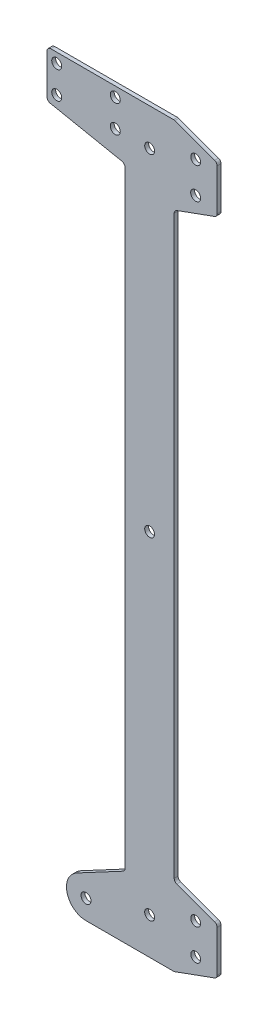
SolidWorks part; units mm, degrees
ref_plane "Front Plane" through (0, 0, 0) normal (0, 0, 1) x (1, 0, 0)
ref_plane "Top Plane" through (0, 0, 0) normal (0, 1, 0) x (1, 0, 0)
ref_plane "Right Plane" through (0, 0, 0) normal (1, 0, 0) x (0, 0, -1)
sketch "Sketch1" plane through (0, 0, 0) normal (0, 0, 1) x (1, 0, 0)
  line L1 (-10, 150) -> (10, 150)
  line L2 (-10, 150) -> (-10, -150)
  line L3 (-10, -150) -> (10, -150)
  line L4 (10, 150) -> (10, -150)
  line L5 (-10, 150) -> (10, -150) construction
  line L6 (-10, -150) -> (10, 150) construction
  point P0 (0, 0)
  dimension "D1" = 300
  dimension "20mm" = 20
extrude "Boss-Extrude1" add sketch "Sketch1" along normal blind 1.5875
sketch "Sketch2" plane through (0, 0, 1.5875) normal (0, 0, 1) x (1, 0, 0)
  line L0 (10, 150) -> (27.4625, 143.65)
  line L1 (27.4625, 143.65) -> (27.4625, 124.6)
  line L2 (27.4625, 124.6) -> (10, 118.25)
  line L3 (10, -150) -> (10, 150) construction
  line L4 (10, 118.25) -> (10, 150)
  line L5 (10, 150) -> (-10, 150) construction
  line L6 (-10, 0) -> (10, 0) construction
  line L7 (-10, 150) -> (-10, -150) construction
  line L8 (10, -118.25) -> (10, -150)
  line L9 (27.4625, -124.6) -> (10, -118.25)
  line L10 (27.4625, -143.65) -> (27.4625, -124.6)
  line L11 (10, -150) -> (27.4625, -143.65)
  line L12 (18.7312, 140.475) -> (18.7313, 127.775) construction
  line L13 (18.7313, -127.775) -> (18.7313, -140.475) construction
  circle A1 centre (18.7313, 127.775) radius 5 construction
  circle A2 centre (18.7312, 140.475) radius 2
  circle A4 centre (18.7313, -127.775) radius 5 construction
  circle A5 centre (18.7313, -127.775) radius 2
  circle A6 centre (18.7312, 134.125) radius 2 construction
  circle A7 centre (18.7313, -134.125) radius 2 construction
  circle A8 centre (18.7313, 127.775) radius 2.032
  circle A9 centre (18.7313, -140.475) radius 2
  point P3 (27.4625, 134.125)
  point P8 (10, 134.125)
  point P13 (18.7312, 121.425)
  point P31 (27.4625, -134.125)
  dimension "D3" = 4
  dimension "D4" = 10
  dimension "D7" = 4.064
  dimension "D1" = 17.4625
  dimension "2.5" = 31.75
  dimension "D2" = 19.05
  dimension "D5" = 9.525
  dimension "D6" = 9.525
  dimension "D8" = 12.7
extrude "Boss-Extrude2" add sketch "Sketch2" against normal up to surface (1.5875 mm away) up to face at (0, 0, 0)
sketch "Sketch4" plane through (0, 0, 1.5875) normal (0, 0, 1) x (1, 0, 0)
  line L0 (0, 150) -> (0, 135) construction
  line L2 (0, 135) -> (0, 0) construction
  line L3 (0, 0) -> (0, -135) construction
  line L4 (0, -135) -> (0, -150) construction
  line L6 (10, 150) -> (-10, 150) construction
  line L7 (-10, -150) -> (10, -150) construction
  circle A0 centre (0, -135) radius 2
  circle A1 centre (0, 0) radius 2
  circle A2 centre (0, 135) radius 2
  dimension "D4" = 4
  dimension "D1" = 15
  dimension "D2" = 135
  dimension "D3" = 135
extrude "Cut-Extrude1" cut sketch "Sketch4" against normal through all
sketch "Sketch5" plane through (0, 0, 1.5875) normal (0, 0, 1) x (1, 0, 0)
  line L0 (-10, 124.6) -> (-41.75, 130.95)
  line L1 (-10, 150) -> (-10, -150) construction
  line L2 (-41.75, 130.95) -> (-41.75, 150)
  line L3 (-41.75, 150) -> (-10, 150)
  line L4 (-10, 150) -> (-10, 124.6)
  line L5 (10, 150) -> (-10, 150) construction
  line L6 (-41.75, 146.0313) -> (-37.7813, 146.0313) construction
  line L7 (-13.9688, 146.0313) -> (-10, 146.0313) construction
  line L8 (-10, -150) -> (-25.875, -150)
  line L9 (-29.6103, -135.0588) -> (-10, -124.6)
  line L10 (-10, -124.6) -> (-10, -150)
  circle A0 centre (-13.9688, 146.0313) radius 2.032
  circle A1 centre (-13.9688, 134.9188) radius 2.032
  circle A2 centre (-37.7813, 146.0313) radius 2.032
  circle A3 centre (-37.7813, 134.9188) radius 2.032
  arc A4 (-25.875, -150) -> (-29.6103, -135.0588) centre (-25.875, -142.0625) cw
  circle A5 centre (-25.875, -142.0625) radius 2.032
  point P24 (-25.875, 150)
  dimension "D5" = 4.064
  dimension "D9" = 4.064
  dimension "D10" = 7.9375
  dimension "D1" = 0
  dimension "D2" = 19.05
  dimension "D3" = 25.4
  dimension "D4" = 31.75
  dimension "D6" = 11.1125
  dimension "D7" = 23.8125
  dimension "D8" = 3.9688
  dimension "D11" = 25.4
extrude "Boss-Extrude3" add sketch "Sketch5" against normal up to surface (1.5875 mm away) up to face at (2, -135, 0)
fillet "Fillet3" radius 1.5875 11 edges at (-10, -124.6, 0.7937) (27.4625, -143.65, 0.7937) (27.4625, -124.6, 0.7937) (10, -118.25, 0.7937) (27.4625, 124.6, 0.7937) (10, 118.25, 0.7937) (27.4625, 143.65, 0.7937) (10, 150, 0.7937) (-10, 124.6, 0.7937) (-41.75, 130.95, 0.7937) (-41.75, 150, 0.7937)
sketch "Sketch6" [suppressed] plane through (0, 0, 3.175) normal (0, 0, 1) x (1, 0, 0)
  line L0 (-10, -124.6) -> (-10, -150) construction
  line L1 (-10, -150) -> (-25.875, -150) construction
  line L2 (-29.6103, -135.0588) -> (-10, -124.6) construction
  line L3 (-10, -124.6) -> (-10, -150)
  line L4 (-10, -150) -> (-25.875, -150)
  line L5 (-29.6103, -135.0588) -> (-10, -124.6)
  circle A0 centre (-25.875, -142.0625) radius 2.032 construction
  arc A1 (-29.6103, -135.0588) -> (-25.875, -150) centre (-25.875, -142.0625) ccw construction
  circle A2 centre (-25.875, -142.0625) radius 2.032
  arc A3 (-29.6103, -135.0588) -> (-25.875, -150) centre (-25.875, -142.0625) ccw
extrude "Boss-Extrude4" [suppressed] add sketch "Sketch6" against normal up to vertex up to point (-10, -123.6475, 0)
fillet "Fillet4" [suppressed] radius 0.7937
fillet "Fillet5" [suppressed] radius 1.5875
sketch "Sketch7" [suppressed] plane through (0, 0, 0) normal (0, 0, -1) x (-1, 0, 0)
  line L0 (-27.1212, 143.7462) -> (-65.2212, 117.3147)
  line L1 (-65.5625, 116.6625) -> (-65.5625, 10.1095)
  line L2 (-63.2093, 7.0427) -> (-10, -7.2147)
  line L4 (-10, -7.2147) -> (-10, 124.044)
  line L5 (-27.4625, 143.094) -> (-27.4625, 131.506) construction
  line L6 (-26.94, 130.76) -> (-10.5225, 124.79) construction
  line L7 (-27.4625, 143.094) -> (-27.4625, 131.506)
  line L8 (-26.94, 130.76) -> (-10.5225, 124.79)
  line L9 (-10, 150) -> (9.2063, 150) construction
  line L10 (-10, 150) -> (9.2063, 150) construction
  line L11 (-48.989, 45.225) -> (-48.989, 48.4) construction
  line L12 (-38.6703, 23) -> (-59.3078, 23) construction
  line L13 (-38.6703, 23) -> (-38.6703, 67.45) construction
  line L14 (-38.6703, 67.45) -> (-59.3078, 67.45) construction
  line L15 (-59.3078, 23) -> (-59.3078, 67.45) construction
  line L16 (-38.6703, 23) -> (-59.3078, 67.45) construction
  line L17 (-38.6703, 67.45) -> (-59.3078, 23) construction
  line L18 (-48.989, 99.2) -> (-48.989, 48.4) construction
  line L19 (-10, -124.044) -> (-10, 124.044) construction
  arc A0 (-65.2212, 117.3147) -> (-65.5625, 116.6625) centre (-64.7688, 116.6625) ccw
  arc A1 (-65.5625, 10.1095) -> (-63.2093, 7.0427) centre (-62.3875, 10.1095) ccw
  arc A2 (-26.94, 143.84) -> (-27.4625, 143.094) centre (-26.6688, 143.094) ccw construction
  arc A3 (-27.4625, 131.506) -> (-26.94, 130.76) centre (-26.6688, 131.506) ccw construction
  arc A4 (-10, 124.044) -> (-10.5225, 124.79) centre (-10.7937, 124.044) ccw construction
  arc A5 (-27.1212, 143.7462) -> (-27.4625, 143.094) centre (-26.6688, 143.094) ccw
  arc A6 (-27.4625, 131.506) -> (-26.94, 130.76) centre (-26.6688, 131.506) ccw
  arc A7 (-10, 124.044) -> (-10.5225, 124.79) centre (-10.7937, 124.044) ccw
  arc A8 (10, 149.2063) -> (9.2063, 150) centre (9.2063, 149.2063) ccw construction
  circle A9 centre (-48.989, 99.2) radius 4.7625
  circle A10 centre (-48.989, 48.4) radius 6.985
  circle A11 centre (-59.3078, 67.45) radius 2.032
  circle A12 centre (-59.3078, 23) radius 2.032
  circle A13 centre (-38.6703, 23) radius 2.032
  circle A14 centre (-38.6703, 67.45) radius 2.032
  circle A15 centre (-18.7312, 10.3) radius 2.032
  point P32 (-48.989, 45.225)
  point P45 (-18.7312, 137.3)
  dimension "D4" = 9.525
  dimension "D6" = 13.97
  dimension "D11" = 4.064
  dimension "D15" = 3.175
  dimension "D1" = 38.1
  dimension "D2" = 106.553
  dimension "D3" = 16.5735
  dimension "D5" = 50.8
  dimension "D7" = 3.175
  dimension "D8" = 44.45
  dimension "D9" = 50.8
  dimension "D10" = 20.6375
  dimension "D12" = 75
  dimension "D13" = 127
  dimension "D14" = 33.3375
extrude "Boss-Extrude5" [suppressed] add sketch "Sketch7" against normal up to surface (3.175 mm away) up to face at (2, -135, 1.5875)
sketch "Sketch8" [suppressed] plane through (0, 0, 3.175) normal (0, 0, 1) x (1, 0, 0)
  line L0 (48.989, 48.4) -> (48.989, 67.45) construction
  line L1 (48.989, 48.4) -> (29.939, 48.4) construction
  line L2 (48.989, 48.4) -> (48.989, 29.35) construction
  line L3 (48.989, 99.2) -> (58.514, 99.2) construction
  line L4 (48.989, 99.2) -> (39.464, 99.2) construction
  line L5 (19.6203, 67.45) -> (19.6203, 54.75) construction
  circle A0 centre (48.989, 67.45) radius 2.032
  circle A1 centre (29.939, 48.4) radius 2.032
  circle A2 centre (48.989, 29.35) radius 2.032
  circle A3 centre (59.3078, 67.45) radius 2.032 construction
  circle A4 centre (58.514, 99.2) radius 2.032
  circle A5 centre (39.464, 99.2) radius 2.032
  circle A6 centre (19.6203, 54.75) radius 2.032
  circle A7 centre (19.6203, 67.45) radius 2.032
  dimension "D2" = 9.525
  dimension "D1" = 19.05
  dimension "D3" = 12.7
  dimension "D4" = 6.35
  dimension "D5" = 10.3187
extrude "Cut-Extrude2" [suppressed] cut sketch "Sketch8" against normal through all
sketch "Sketch9" [suppressed] plane through (0, 0, 0) normal (0, 0, -1) x (-1, 0, 0)
  line L0 (-27.2321, 143.6532) -> (-60.2559, 110.3836)
  line L2 (-65.5625, 86.5) -> (-64.8416, 100.0438)
  line L3 (-65.5625, 86.5) -> (-65.5625, 116.6625)
  line L4 (-27.1212, 143.7462) -> (-65.2212, 117.3147) construction
  line L5 (-27.1212, 143.7462) -> (-65.2212, 117.3147)
  line L6 (-65.5625, 116.6625) -> (-65.5625, 10.1095) construction
  arc A0 (-26.94, 143.84) -> (-27.1212, 143.7462) centre (-26.6688, 143.094) ccw construction
  arc A1 (-27.1212, 143.7462) -> (-27.2321, 143.6532) centre (-26.6688, 143.094) ccw
  arc A2 (-60.2559, 110.3836) -> (-64.8416, 100.0438) centre (-48.989, 99.2) ccw
  arc A4 (-65.2212, 117.3147) -> (-65.5625, 116.6625) centre (-64.7688, 116.6625) ccw construction
  arc A5 (-65.2212, 117.3147) -> (-65.5625, 116.6625) centre (-64.7688, 116.6625) ccw
  circle A6 centre (-59.3078, 67.45) radius 2.032 construction
  dimension "D1" = 15.875
  dimension "D2" = 19.05
extrude "Cut-Extrude3" [suppressed] cut sketch "Sketch9" against normal through all
sketch "Sketch10" [suppressed] plane through (0, 0, 0) normal (0, 0, -1) x (-1, 0, 0)
  line L0 (-59.2125, 84.9125) -> (-46.5125, 84.9125) construction
  line L1 (-65.5625, 86.5) -> (-65.5625, 10.1095) construction
  circle A0 centre (-59.2125, 84.9125) radius 2.032
  circle A1 centre (-46.5125, 84.9125) radius 2.032
  circle A2 centre (-59.3078, 67.45) radius 2.032 construction
  point P6 (-48.989, 67.45)
  dimension "D1" = 12.7
  dimension "D2" = 17.4625
  dimension "D3" = 6.35
extrude "Cut-Extrude4" [suppressed] cut sketch "Sketch10" against normal through all
